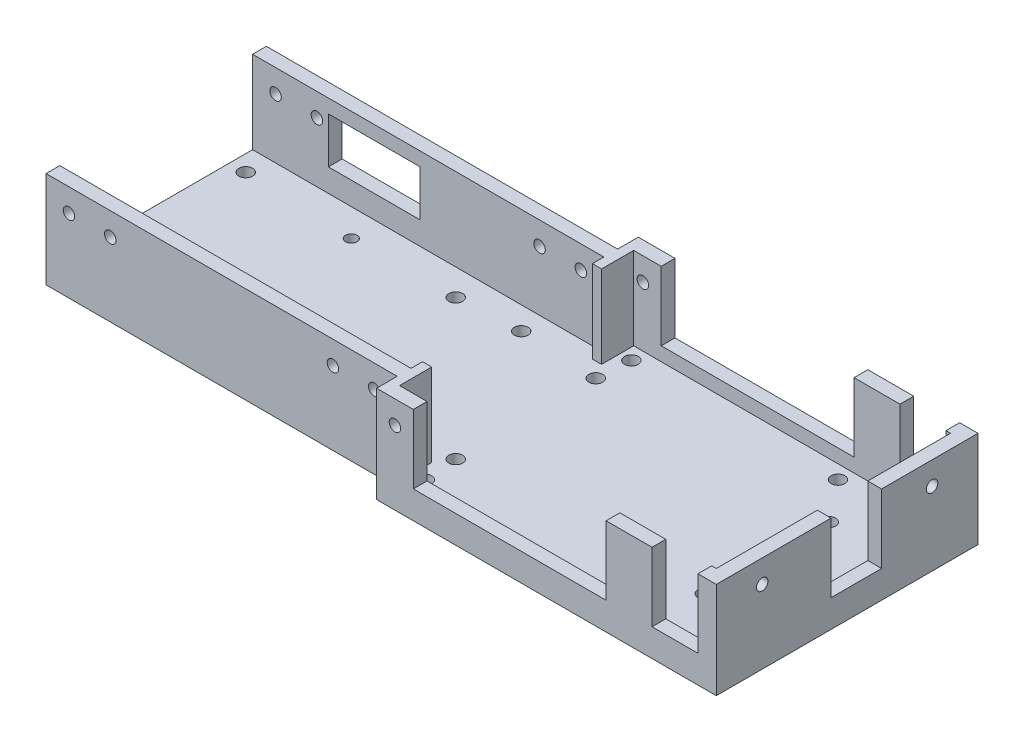
SolidWorks part; units mm, degrees
ref_plane "Front Plane" through (0, 0, 0) normal (0, 0, 1) x (1, 0, 0)
ref_plane "Top Plane" through (0, 0, 0) normal (0, 1, 0) x (1, 0, 0)
ref_plane "Right Plane" through (0, 0, 0) normal (1, 0, 0) x (0, 0, -1)
sketch "Sketch1" plane through (0, 0, 0) normal (0, 1, 0) x (1, 0, 0)
  line L1 (-115.1205, 21.9093) -> (35.3795, 21.9093)
  line L2 (-115.1205, 21.9093) -> (-115.1205, -26.0907)
  line L3 (-115.1205, -26.0907) -> (35.3795, -26.0907)
  line L4 (35.3795, 21.9093) -> (35.3795, -26.0907)
  dimension "D1" = 150.5
  dimension "D2" = 48
extrude "Boss-Extrude1" add sketch "Sketch1" along normal blind 3
sketch "Sketch2" plane through (0, 3, 0) normal (0, 1, 0) x (1, 0, 0)
  line L1 (35.3795, 21.9093) -> (-115.1205, 21.9093) construction
  line L2 (35.3795, -26.0907) -> (35.3795, 21.9093) construction
  line L3 (-115.1205, -26.0907) -> (35.3795, -26.0907) construction
  circle A0 centre (-65.1205, 13.1593) radius 1.5
  circle A1 centre (-65.1205, -17.3407) radius 1.5
  circle A2 centre (-34.6205, -17.3407) radius 1.5
  circle A3 centre (-34.6205, 13.1593) radius 1.5
  circle A6 centre (17.8795, -15.5907) radius 1.5
  circle A7 centre (17.8795, 11.4093) radius 1.5
  circle A8 centre (-111.6205, -18.0907) radius 1.5
  circle A9 centre (-111.6205, 13.9093) radius 1.5
  circle A13 centre (-87.6205, 12.9093) radius 1.25
  circle A14 centre (-87.6205, -17.0907) radius 1.25
  circle A15 centre (-51.6205, 13.9093) radius 1.5
  circle A16 centre (-51.6205, -18.0907) radius 1.5
  point P38 (0, 0)
  point P39 (0, 0)
  point P42 (0, 0)
  dimension "D1" = 3
  dimension "D2" = 3
  dimension "D3" = 3
  dimension "D4" = 3
  dimension "D13" = 17.5
  dimension "D14" = 17.5
  dimension "D19" = 3
  dimension "D20" = 3
  dimension "D25" = 3
  dimension "D26" = 3
  dimension "D37" = 2.5
  dimension "D38" = 2.5
  dimension "D43" = 3
  dimension "D44" = 3
  dimension "D5" = 52.5
  dimension "D6" = 8.75
  dimension "D7" = 52.5
  dimension "D8" = 30.5
  dimension "D9" = 30.5
  dimension "D10" = 30.5
  dimension "D11" = 8.75
  dimension "D12" = 30.5
  dimension "D15" = 17
  dimension "D16" = 17
  dimension "D17" = 22.5
  dimension "D18" = 22.5
  dimension "D23" = 27
  dimension "D24" = 10.5
  dimension "D27" = 32
  dimension "D28" = 8
  dimension "D39" = 30
  dimension "D42" = 9
  dimension "D45" = 60
  dimension "D46" = 60
  dimension "D47" = 32
  dimension "D48" = 8
extrude "Cut-Extrude1" cut sketch "Sketch2" against normal through all
sketch "Sketch4" plane through (0, 3, 0) normal (0, 1, 0) x (1, 0, 0)
  line L0 (35.3795, 21.9093) -> (-115.1205, 21.9093) construction
  line L1 (-38.6205, 26.4093) -> (35.3795, 26.4093)
  line L2 (-38.6205, 26.4093) -> (-38.6205, 21.9093)
  line L3 (-38.6205, 21.9093) -> (35.3795, 21.9093)
  line L4 (35.3795, 26.4093) -> (35.3795, 21.9093)
  line L5 (-38.6205, -26.0907) -> (35.3795, -26.0907)
  line L6 (-38.6205, -26.0907) -> (-38.6205, -30.5907)
  line L7 (-38.6205, -30.5907) -> (35.3795, -30.5907)
  line L8 (35.3795, -26.0907) -> (35.3795, -30.5907)
  line L9 (-115.1205, -26.0907) -> (35.3795, -26.0907) construction
  line L10 (35.3795, -26.0907) -> (35.3795, 21.9093) construction
  point P14 (35.3795, -28.3407)
  line M26 (-115.1205, -26.0907) -> (35.3795, -26.0907)
  dimension "D1" = 74
  dimension "D2" = 4.5
  dimension "D3" = 74
  dimension "D4" = 4.5
  dimension "D5" = 0
  dimension "D6" = 0
  dimension "D7" = 0
  dimension "D8" = 0
extrude "Boss-Extrude2" add sketch "Sketch4" against normal blind 3 contours L8 L6 L7 M26 | L2 L1 L4 L3 region at (-1.6205, 3, 28.3407)
sketch "Sketch5" plane through (0, 3, 0) normal (0, 1, 0) x (1, 0, 0)
  line L0 (-38.6205, -30.5907) -> (35.3795, -30.5907) construction
  line L1 (-38.6205, 26.4093) -> (-38.6205, 21.9093) construction
  line L4 (-38.6205, -26.0907) -> (-38.6205, -30.5907) construction
  line L8 (-38.6205, 26.4093) -> (35.3795, 26.4093) construction
  circle A0 centre (-34.1205, 20.4093) radius 1.5
  circle A1 centre (-34.1205, -24.5907) radius 1.5
  circle A2 centre (10.8795, 20.4093) radius 1.5
  circle A3 centre (10.8795, -24.5907) radius 1.5
  dimension "D1" = 3
  dimension "D2" = 3
  dimension "D3" = 3
  dimension "D4" = 3
  dimension "D5" = 45
  dimension "D6" = 45
  dimension "D7" = 45
  dimension "D8" = 45
  dimension "D9" = 6
  dimension "D10" = 4.5
  dimension "D11" = 4.5
  dimension "D12" = 6
extrude "Cut-Extrude3" cut sketch "Sketch5" against normal through all
sketch "Sketch6" plane through (0, 3, 0) normal (0, 1, 0) x (1, 0, 0)
  line L0 (31.3795, 26.4093) -> (35.3795, 26.4093)
  line L5 (31.3795, 26.4093) -> (31.3795, 23.4093)
  line L6 (31.3795, 23.4093) -> (35.3795, 23.4093)
  line L7 (35.3795, 26.4093) -> (35.3795, 23.4093)
  line L8 (31.3795, -27.5907) -> (35.3795, -27.5907)
  line L9 (31.3795, -27.5907) -> (31.3795, -30.5907)
  line L10 (31.3795, -30.5907) -> (35.3795, -30.5907)
  line L11 (35.3795, -27.5907) -> (35.3795, -30.5907)
  line L12 (32.3795, 23.4093) -> (35.3795, 23.4093)
  line L13 (32.3795, 23.4093) -> (32.3795, 5.4093)
  line L14 (32.3795, 5.4093) -> (35.3795, 5.4093)
  line L15 (35.3795, 23.4093) -> (35.3795, 5.4093)
  line L16 (32.3795, -5.5907) -> (35.3795, -5.5907)
  line L17 (32.3795, -5.5907) -> (32.3795, -27.5907)
  line L18 (32.3795, -27.5907) -> (35.3795, -27.5907)
  line L19 (35.3795, -5.5907) -> (35.3795, -27.5907)
  line L20 (35.3795, -30.5907) -> (35.3795, 26.4093) construction
  line L21 (-38.6205, 26.4093) -> (35.3795, 26.4093) construction
  line L22 (11.3795, 26.4093) -> (21.3795, 26.4093)
  line L23 (-38.6205, -30.5907) -> (35.3795, -30.5907) construction
  line L24 (-38.6205, 26.4093) -> (-30.6205, 26.4093)
  line L25 (-38.6205, 26.4093) -> (-38.6205, 23.4093)
  line L26 (-38.6205, 23.4093) -> (-30.6205, 23.4093)
  line L27 (-30.6205, 26.4093) -> (-30.6205, 23.4093)
  line L28 (-38.6205, 23.4093) -> (-36.6205, 23.4093)
  line L29 (-38.6205, 23.4093) -> (-38.6205, 16.4093)
  line L30 (-38.6205, 16.4093) -> (-36.6205, 16.4093)
  line L31 (-36.6205, 23.4093) -> (-36.6205, 16.4093)
  line L32 (-38.6205, -20.5907) -> (-36.6205, -20.5907)
  line L33 (-38.6205, -20.5907) -> (-38.6205, -27.5907)
  line L34 (-38.6205, -27.5907) -> (-36.6205, -27.5907)
  line L35 (-36.6205, -20.5907) -> (-36.6205, -27.5907)
  line L36 (-38.6205, -27.5907) -> (-30.6205, -27.5907)
  line L37 (-38.6205, -27.5907) -> (-38.6205, -30.5907)
  line L38 (-38.6205, -30.5907) -> (-30.6205, -30.5907)
  line L39 (-30.6205, -27.5907) -> (-30.6205, -30.5907)
  line L40 (-38.6205, 26.4093) -> (-38.6205, 21.9093) construction
  line L41 (-38.6205, -26.0907) -> (-38.6205, -30.5907) construction
  line L42 (11.3795, 26.4093) -> (11.3795, 23.4093)
  line L43 (11.3795, 23.4093) -> (21.3795, 23.4093)
  line L44 (-38.6205, 21.9093) -> (-115.1205, 21.9093) construction
  line L45 (-115.1205, 21.9093) -> (-38.6205, 21.9093)
  line L46 (-115.1205, 21.9093) -> (-115.1205, 18.9093)
  line L47 (-115.1205, 18.9093) -> (-38.6205, 18.9093)
  line L48 (-38.6205, 21.9093) -> (-38.6205, 18.9093)
  line L49 (-115.1205, -26.0907) -> (-38.6205, -26.0907) construction
  line L50 (-115.1205, -23.0907) -> (-38.6205, -23.0907)
  line L51 (-115.1205, -23.0907) -> (-115.1205, -26.0907)
  line L52 (-115.1205, -26.0907) -> (-38.6205, -26.0907)
  line L53 (-38.6205, -23.0907) -> (-38.6205, -26.0907)
  line L54 (21.3795, 26.4093) -> (21.3795, 23.4093)
  line L55 (11.3795, -27.5907) -> (21.3795, -27.5907)
  line L56 (11.3795, -27.5907) -> (11.3795, -30.5907)
  line L57 (11.3795, -30.5907) -> (21.3795, -30.5907)
  line L58 (21.3795, -27.5907) -> (21.3795, -30.5907)
  line L59 (11.1449, -22.8352) -> (21.1449, -22.8352)
  line L60 (11.1449, -22.8352) -> (11.1449, -25.8352)
  line L61 (11.1449, -25.8352) -> (21.1449, -25.8352)
  line L62 (21.1449, -22.8352) -> (21.1449, -25.8352)
  line L63 (-115.1205, 21.9093) -> (-115.1205, -26.0907) construction
  point P24 (35.3795, 24.9093)
  line M45 (35.3795, -30.5907) -> (35.3795, 26.4093)
  line M46 (35.3795, 26.4093) -> (-38.6205, 26.4093)
  dimension "D13" = 18
  dimension "D20" = 3
  dimension "D1" = 0
  dimension "D2" = 0
  dimension "D3" = 0
  dimension "D4" = 3
  dimension "D5" = 4
  dimension "D6" = 0
  dimension "D7" = 0
  dimension "D8" = 0
  dimension "D9" = 3
  dimension "D10" = 4
  dimension "D11" = 0
  dimension "D12" = 0
  dimension "D14" = 3
  dimension "D15" = 3
  dimension "D16" = 8
  dimension "D17" = 3
  dimension "D18" = 0
  dimension "D19" = 0
  dimension "D21" = 8
  dimension "D22" = 0
  dimension "D23" = 0
  dimension "D24" = 2
  dimension "D25" = 2
  dimension "D26" = 7
  dimension "D27" = 7
  dimension "D28" = 0
  dimension "D29" = 0
  dimension "D30" = 0
  dimension "D31" = 0
  dimension "D32" = 0
  dimension "D33" = 3
  dimension "D34" = 0
  dimension "D35" = 0
  dimension "D36" = 0
  dimension "D37" = 3
  dimension "D38" = 0
  dimension "D39" = 0
  dimension "D40" = 0
  dimension "D41" = 10
  dimension "D42" = 10
  dimension "D43" = 3
  dimension "D44" = 0
  dimension "D45" = 10
  dimension "D46" = 10
  dimension "D47" = 3
extrude "Boss-Extrude3" add sketch "Sketch6" along normal blind 18 contours L5 L6 M45 M46 | L50 L53 L52 L51 | L45 L48 L47 L46 | L24 L27 L26 L25 | L36 L39 L38 L37 | L33 L34 L35 L32 | L31 L30 L29 L28 | L11 L10 L9 L8 | L19 L18 L17 L16 | L15 L14 L13 L12 | L55 L58 L57 L56 | L22 L54 L43 L42 region at (33.3795, 3, -24.9093)
sketch "Sketch8" plane through (0, 3, 0) normal (0, 1, 0) x (1, 0, 0)
  line L0 (21.3795, -27.5907) -> (31.3795, -27.5907)
  line L5 (21.3795, -27.5907) -> (21.3795, -30.5907)
  line L6 (21.3795, -30.5907) -> (31.3795, -30.5907)
  line L7 (31.3795, -27.5907) -> (31.3795, -30.5907)
  line L8 (31.3795, -27.5907) -> (31.3795, -30.5907) construction
  line L9 (21.3795, -30.5907) -> (31.3795, -30.5907) construction
  line L11 (21.3795, -27.5907) -> (21.3795, -30.5907) construction
  line L12 (21.3795, 26.4093) -> (31.3795, 26.4093)
  line L13 (21.3795, 26.4093) -> (21.3795, 23.4093)
  line L14 (21.3795, 23.4093) -> (31.3795, 23.4093)
  line L15 (31.3795, 26.4093) -> (31.3795, 23.4093)
  line L16 (21.3795, 26.4093) -> (31.3795, 26.4093) construction
  line L17 (21.3795, 26.4093) -> (21.3795, 23.4093) construction
  line L18 (31.3795, 26.4093) -> (31.3795, 23.4093) construction
  line L19 (-30.6205, 26.4093) -> (11.3795, 26.4093)
  line L20 (-30.6205, 26.4093) -> (-30.6205, 23.4093)
  line L21 (-30.6205, 23.4093) -> (11.3795, 23.4093)
  line L22 (11.3795, 26.4093) -> (11.3795, 23.4093)
  line L23 (-30.6205, 26.4093) -> (11.3795, 26.4093) construction
  line L24 (11.3795, 26.4093) -> (11.3795, 23.4093) construction
  line L25 (-30.6205, 26.4093) -> (-30.6205, 23.4093) construction
  line L26 (-30.6205, -27.5907) -> (11.3795, -27.5907)
  line L27 (-30.6205, -27.5907) -> (-30.6205, -30.5907)
  line L28 (-30.6205, -30.5907) -> (11.3795, -30.5907)
  line L29 (11.3795, -27.5907) -> (11.3795, -30.5907)
  line L30 (-30.6205, -30.5907) -> (11.3795, -30.5907) construction
  line L31 (-30.6205, -27.5907) -> (-30.6205, -30.5907) construction
  line L32 (11.3795, -27.5907) -> (11.3795, -30.5907) construction
  line L33 (32.3795, 5.4093) -> (35.3795, 5.4093)
  line L34 (32.3795, 5.4093) -> (32.3795, -5.5907)
  line L35 (32.3795, -5.5907) -> (35.3795, -5.5907)
  line L36 (35.3795, 5.4093) -> (35.3795, -5.5907)
  line L38 (35.3795, -5.5907) -> (35.3795, 5.4093) construction
  line L39 (32.3795, 5.4093) -> (35.3795, 5.4093) construction
  line L40 (32.3795, -5.5907) -> (35.3795, -5.5907) construction
  point P8 (31.3795, -29.0907)
  point P15 (31.3795, 24.9093)
  point P26 (11.3795, 24.9093)
  point P37 (11.3795, -29.0907)
  point P48 (35.3795, -0.0907)
  dimension "D1" = 3
  dimension "D2" = 0
  dimension "D3" = 0
  dimension "D4" = 0
  dimension "D5" = 0
  dimension "D6" = 0
  dimension "D7" = 0
  dimension "D8" = 0
  dimension "D9" = 3
  dimension "D10" = 0
  dimension "D11" = 0
  dimension "D12" = 0
  dimension "D13" = 3
  dimension "D14" = 0
  dimension "D15" = 0
  dimension "D16" = 3
  dimension "D17" = 0
  dimension "D18" = 0
  dimension "D19" = 0
extrude "Boss-Extrude4" add sketch "Sketch8" along normal blind 3
sketch "Sketch9" plane through (0, 0, -21.9093) normal (0, 0, -1) x (-1, 0, 0)
  line L0 (38.6205, 0) -> (115.1205, 0) construction
  line L1 (98.6205, 8) -> (78.6205, 8)
  line L2 (98.6205, 8) -> (98.6205, 18)
  line L3 (98.6205, 18) -> (78.6205, 18)
  line L4 (78.6205, 8) -> (78.6205, 18)
  line L6 (38.6205, 0) -> (38.6205, 21) construction
  dimension "D1" = 20
  dimension "D2" = 10
  dimension "D3" = 8
  dimension "D4" = 40
extrude "Cut-Extrude4" cut sketch "Sketch9" against normal up to next
sketch "Sketch10" plane through (35.3795, 0, 0) normal (1, 0, 0) x (0, 0, -1)
  line L0 (-5.5907, 21) -> (-30.5907, 21) construction
  line L1 (-30.5907, 0) -> (-30.5907, 21) construction
  line L2 (26.4093, 0) -> (26.4093, 21) construction
  line L3 (26.4093, 21) -> (5.4093, 21) construction
  circle A0 centre (-20.5907, 16) radius 1.25
  circle A1 centre (16.4093, 16) radius 1.25
  point P10 (0, 0)
  point P12 (14.1316, 20.5452)
  dimension "D1" = 2.5
  dimension "D2" = 2.5
  dimension "D3" = 5
  dimension "D4" = 10
  dimension "D5" = 10
  dimension "D6" = 5
extrude "Cut-Extrude5" cut sketch "Sketch10" against normal up to next
sketch "Sketch11" plane through (0, 0, -21.9093) normal (0, 0, -1) x (-1, 0, 0)
  line L0 (115.1205, 21) -> (38.6205, 21) construction
  line L1 (38.6205, 0) -> (38.6205, 21) construction
  line L2 (115.1205, 21) -> (115.1205, 0) construction
  circle A0 centre (43.6205, 16) radius 1.25
  circle A1 centre (110.1205, 16) radius 1.25
  circle A2 centre (52.6205, 16) radius 1.25
  circle A3 centre (101.1205, 16) radius 1.25
  dimension "D1" = 2.5
  dimension "D2" = 2.5
  dimension "D7" = 2.5
  dimension "D10" = 2.5
  dimension "D3" = 5
  dimension "D4" = 5
  dimension "D5" = 5
  dimension "D6" = 5
  dimension "D8" = 5
  dimension "D9" = 14
  dimension "D11" = 14
  dimension "D12" = 5
extrude "Cut-Extrude6" cut sketch "Sketch11" against normal through all
sketch "Sketch12" plane through (0, 0, -26.4093) normal (0, 0, -1) x (-1, 0, 0)
  line L0 (38.6205, 21) -> (30.6205, 21) construction
  line L2 (38.6205, 0) -> (38.6205, 21) construction
  circle A0 centre (34.6205, 16) radius 1.25
  dimension "D1" = 2.5
  dimension "D2" = 5
  dimension "D3" = 4
extrude "Cut-Extrude7" cut sketch "Sketch12" against normal through all
